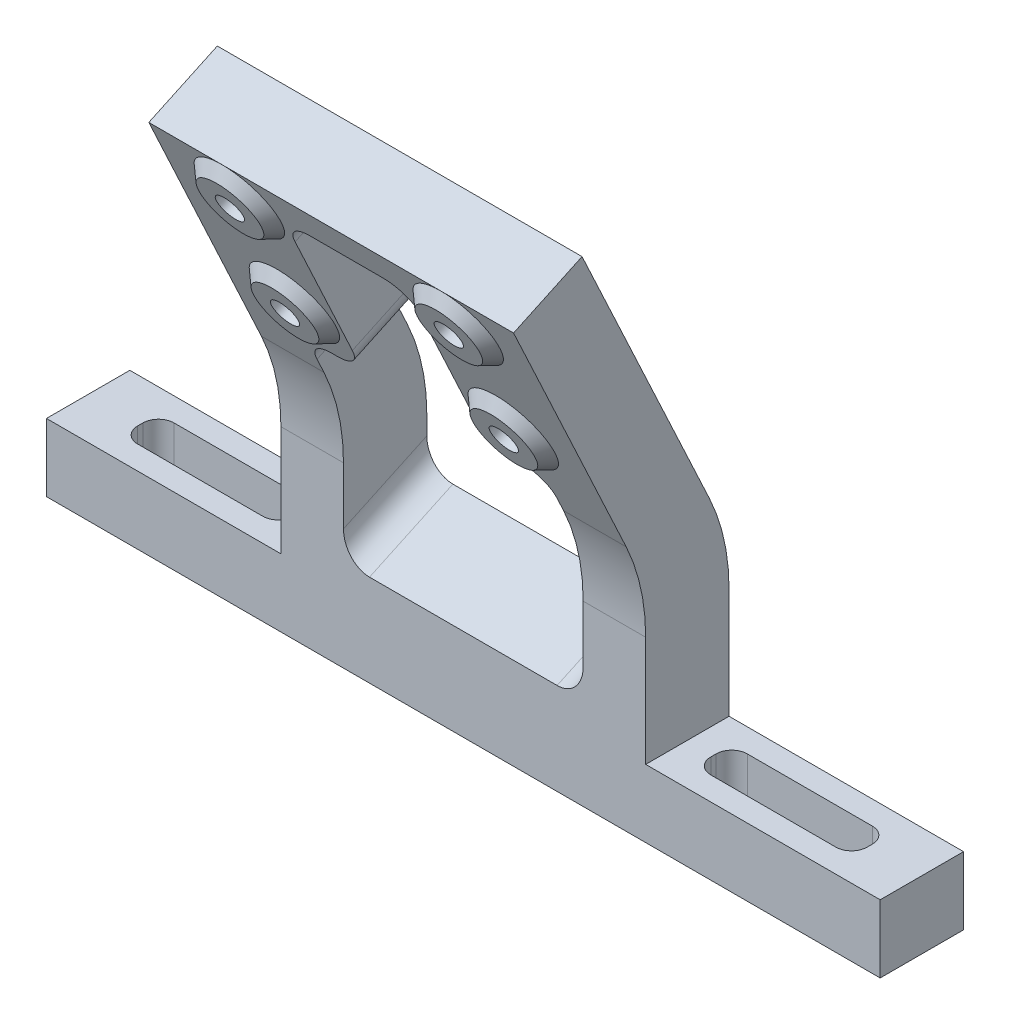
SolidWorks part; units mm, degrees
ref_plane "Front Plane" through (0, 0, 0) normal (0, 0, 1) x (1, 0, 0)
ref_plane "Top Plane" through (0, 0, 0) normal (0, 1, 0) x (1, 0, 0)
ref_plane "Right Plane" through (0, 0, 0) normal (1, 0, 0) x (0, 0, -1)
sketch "Sketch13" plane through (0, 0, 0) normal (0, 1, 0) x (1, 0, 0)
  line L1 (-40, -4) -> (40, -4)
  line L2 (-40, -4) -> (-40, 4)
  line L3 (-40, 4) -> (40, 4)
  line L4 (40, -4) -> (40, 4)
  line L5 (-40, -4) -> (40, 4) construction
  line L6 (-40, 4) -> (40, -4) construction
  point P0 (0, 0)
  dimension "D1" = 80
  dimension "D2" = 8
extrude "Boss-Extrude9" add sketch "Sketch13" along normal blind 6.5 contours L2 L3 L4 L1
sketch "Sketch14" plane through (0, 6.5, 0) normal (0, 1, 0) x (1, 0, 0)
  line L0 (-20, 0) -> (0, 0) construction
  line L1 (0, 0) -> (20, 0) construction
  line L2 (-35, -1.75) -> (-20, -1.75)
  line L3 (-35, -1.75) -> (-35, 1.75)
  line L4 (-35, 1.75) -> (-20, 1.75)
  line L5 (-20, -1.75) -> (-20, 1.75)
  line L6 (-35, -1.75) -> (-20, 1.75) construction
  line L7 (-35, 1.75) -> (-20, -1.75) construction
  line L8 (20, -1.75) -> (35, -1.75)
  line L9 (20, -1.75) -> (20, 1.75)
  line L10 (20, 1.75) -> (35, 1.75)
  line L11 (35, -1.75) -> (35, 1.75)
  line L12 (20, -1.75) -> (35, 1.75) construction
  line L13 (20, 1.75) -> (35, -1.75) construction
  point P3 (-27.5, 0)
  point P8 (27.5, 0)
  dimension "D1" = 15
  dimension "D2" = 20
  dimension "D3" = 3.5
extrude "Cut-Extrude1" cut sketch "Sketch14" against normal through all
sketch "Sketch15" plane through (0, 6.5, 0) normal (0, 1, 0) x (1, 0, 0)
  line L0 (-40, 4) -> (40, 4) construction
  line L1 (-17.5, -4) -> (17.5, -4)
  line L2 (-17.5, -4) -> (-17.5, 4)
  line L3 (-17.5, 4) -> (17.5, 4)
  line L4 (17.5, -4) -> (17.5, 4)
  line L5 (-17.5, -4) -> (17.5, 4) construction
  line L6 (-17.5, 4) -> (17.5, -4) construction
  point P0 (0, 0)
  dimension "D1" = 35
extrude "Boss-Extrude10" add sketch "Sketch15" along normal blind 15
sketch "Sketch16" plane through (-17.5, 0, 0) normal (-1, 0, 0) x (0, 0, 1)
  line L0 (4, 21.5) -> (16.6785, 48.6892)
  line L1 (-4, 21.5) -> (10.1074, 51.7534)
  line L2 (10.1074, 51.7534) -> (16.6785, 48.6892)
  line L3 (-4, 21.5) -> (4, 21.5) construction
  line L8 (-4, 6.5) -> (4, 6.5)
  line L9 (4, 6.5) -> (4, 21.5)
  line L10 (4, 21.5) -> (-4, 21.5)
  line L11 (-4, 21.5) -> (-4, 6.5)
  line L14 (4, 21.5) -> (-4, 21.5)
  dimension "D1" = 115
  dimension "D2" = 30
  dimension "D3" = 0
extrude "Boss-Extrude11" add sketch "Sketch16" against normal up to surface (35 mm away) up to face at (17.5, 14, 0)
sketch "Sketch17" plane through (0, 2.3079, -4.9494) normal (0, -0.4226, 0.9063) x (1, 0, 0)
  line L0 (-17.5, 40.9261) -> (17.5, 40.9261) construction
  line L1 (-17.5, 21.1761) -> (-17.5, 51.1761) construction
  line L2 (17.5, 51.1761) -> (17.5, 21.1761) construction
  line L4 (-10.5, 34.6761) -> (10.5, 34.6761) construction
  line L5 (-10.5, 34.6761) -> (-10.5, 47.1761) construction
  line L6 (-10.5, 47.1761) -> (10.5, 47.1761) construction
  line L7 (10.5, 34.6761) -> (10.5, 47.1761) construction
  line L8 (-10.5, 34.6761) -> (10.5, 47.1761) construction
  line L9 (-10.5, 47.1761) -> (10.5, 34.6761) construction
  line L10 (17.5, 51.1761) -> (-17.5, 51.1761) construction
  circle A0 centre (-10.5, 47.1761) radius 3
  circle A1 centre (10.5, 47.1761) radius 3
  circle A2 centre (10.5, 34.6761) radius 3
  circle A3 centre (-10.5, 34.6761) radius 3
  point P6 (0, 40.9261)
  dimension "D3" = 6
  dimension "D1" = 21
  dimension "D2" = 12.5
  dimension "D4" = 4
extrude "Boss-Extrude12" add sketch "Sketch17" along normal blind 1
sketch "Sketch20" plane through (0, 1.8853, -4.0431) normal (0, -0.4226, 0.9063) x (1, 0, 0)
  circle A4 centre (-10.5, 47.1761) radius 1.3
  circle A5 centre (10.5, 47.1761) radius 1.3
  circle A7 centre (10.5, 34.6761) radius 1.3
  circle A8 centre (-10.5, 34.6761) radius 1.3
  circle A9 centre (-10.5, 34.6761) radius 3 construction
  circle A10 centre (-10.5, 47.1761) radius 3 construction
  circle A11 centre (10.5, 47.1761) radius 3 construction
  circle A12 centre (10.5, 34.6761) radius 3 construction
  dimension "D1" = 2.6
extrude "Cut-Extrude2" cut sketch "Sketch20" against normal through all
sketch "Sketch21" plane through (0, 2.3079, -4.9494) normal (0, -0.4226, 0.9063) x (1, 0, 0)
  line L1 (-11.5, 9.6761) -> (11.5, 9.6761)
  line L2 (-11.5, 9.6761) -> (-11.5, 29.6761)
  line L3 (-11.5, 29.6761) -> (11.5, 29.6761)
  line L4 (11.5, 9.6761) -> (11.5, 29.6761)
  line L5 (-11.5, 9.6761) -> (11.5, 29.6761) construction
  line L6 (-11.5, 29.6761) -> (11.5, 9.6761) construction
  line L7 (-17.5, 21.1761) -> (17.5, 21.1761) construction
  circle A0 centre (10.5, 34.6761) radius 1.3 construction
  point P0 (0, 21.1761)
  point P10 (0, 19.6761)
  point P16 (0, 21.1761)
  dimension "D1" = 23
  dimension "D2" = 20
  dimension "D3" = 5
extrude "Cut-Extrude3" cut sketch "Sketch21" against normal through all both and the other way through all
sketch "Sketch22" plane through (0, 2.3079, -4.9494) normal (0, -0.4226, 0.9063) x (1, 0, 0)
  line L0 (11.5, 29.6761) -> (-11.5, 29.6761) construction
  line L1 (-6, 47.6761) -> (6, 47.6761)
  line L2 (-6, 47.6761) -> (-6, 29.6761)
  line L3 (-6, 29.6761) -> (6, 29.6761)
  line L4 (6, 47.6761) -> (6, 29.6761)
  line L5 (-6, 47.6761) -> (6, 29.6761) construction
  line L6 (-6, 29.6761) -> (6, 47.6761) construction
  point P0 (0, 38.6761)
  point P9 (0, 29.6761)
  point P14 (0, 29.6761)
  dimension "D1" = 12
  dimension "D2" = 18
extrude "Cut-Extrude4" cut sketch "Sketch22" against normal through all
fillet "Fillet2" radius 1.5 8 edges at (35, 3.25, -1.75) (35, 3.25, 1.75) (20, 3.25, 1.75) (20, 3.25, -1.75) (-35, 3.25, -1.75) (-35, 3.25, 1.75) (-20, 3.25, 1.75) (-20, 3.25, -1.75)
chamfer "Chamfer1" distance 1 angle 45 4 edges at (10.5, 31.0162, 8.4375) (10.5, 42.3451, 13.7202) (-10.5, 42.3451, 13.7202) (-10.5, 31.0162, 8.4375)
fillet "Fillet3" radius 20 4 edges at (-14.5, 21.5, -4) (14.5, 21.5, -4) (14.5, 21.5, 4) (-14.5, 21.5, 4)
fillet "Fillet4" radius 2.5 8 edges at (6, 47.0492, 11.9138) (-6, 47.0492, 11.9138) (11.5, 30.7357, 4.3067) (-11.5, 30.7357, 4.3067) (6, 30.7357, 4.3067) (-6, 30.7357, 4.3067) (11.5, 10.6764, 0) (-11.5, 10.6764, 0)
